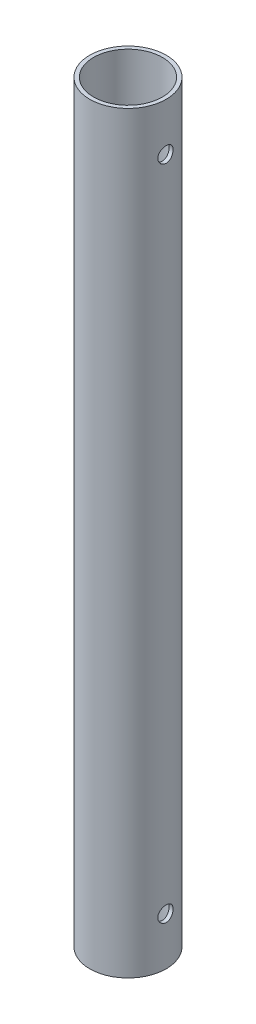
SolidWorks part; units mm, degrees
material "1060 Alloy"
ref_plane "Front" through (0, 0, 0) normal (0, 0, 1) x (1, 0, 0)
ref_plane "Top" through (0, 0, 0) normal (0, 1, 0) x (1, 0, 0)
ref_plane "Right" through (0, 0, 0) normal (1, 0, 0) x (0, 0, -1)
sketch "Sketch1" plane through (0, 0, 0) normal (0, 1, 0) x (1, 0, 0)
  circle A0 centre (0, 0) radius 10
  circle A1 centre (0, 0) radius 9
  dimension "D1" = 20
  dimension "D2" = 1
extrude "Boss-Extrude1" add sketch "Sketch1" along normal blind 197
ref_plane "Plane1" through (10, 0, 0) normal (1, 0, 0) x (0, 0, -1)
sketch "Sketch2" plane through (10, 0, 0) normal (1, 0, 0) x (0, 0, -1)
  line L0 (0, 197) -> (0, 0) construction
  line L6 (9, 197) -> (-9, 197) construction
  circle A0 centre (0, 184.5) radius 2
  circle A1 centre (0, 12.5) radius 2
  dimension "D1" = 4
  dimension "D3" = 4
  dimension "D2" = 12.5
  dimension "D4" = 12.5
extrude "Cut-Extrude1" cut sketch "Sketch2" against normal through all contours L0 A0 | L0 A1 | A1 L0 | A0 L0 region at (10, 184.5, -0.8488) region at (10, 12.5, -0.8488) region at (10, 12.5, 0.8488) region at (10, 184.5, 0.8488)
